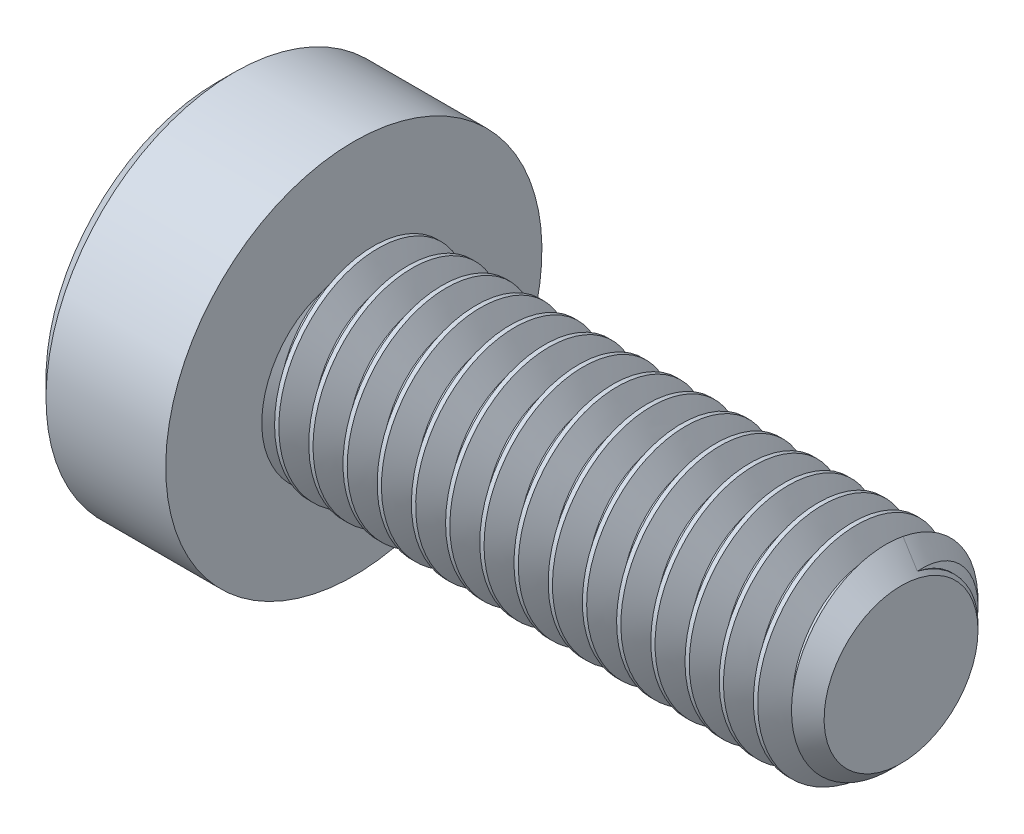
SolidWorks part; units mm, degrees
ref_plane "Front Plane" through (0, 0, 0) normal (0, 0, 1) x (1, 0, 0)
ref_plane "Top Plane" through (0, 0, 0) normal (0, 1, 0) x (1, 0, 0)
ref_plane "Right Plane" through (0, 0, 0) normal (1, 0, 0) x (0, 0, -1)
sketch "Sketch1" plane through (0, 0, 0) normal (0, 0, 1) x (1, 0, 0)
  line L0 (4, 0) -> (-4, 0) construction
  line L1 (4, 1.5) -> (4, -1.5) construction
  line L2 (-4, 2.75) -> (-4, -2.75) construction
  line L3 (-4, 2.75) -> (-5.75, 2.75) construction
  line L4 (-5.75, 2.75) -> (-6, 2.5) construction
  line L5 (-6, 2.5) -> (-6, -2.5) construction
  line L6 (-6, -2.5) -> (-5.75, -2.75) construction
  line L7 (-5.75, -2.75) -> (-4, -2.75) construction
  point P7 (-4.38, 0)
  point P12 (2, -1.5)
  dimension "D1" = 45
  dimension "Dec." = 3
  dimension "Length" = 8
  dimension "Head Dia" = 5.5
  dimension "Head Height" = 2
  dimension "Hex Depth" = 1.62
  dimension "Chamfer" = 0.25
  dimension "D2" = 2
ref_plane "Plane1" through (4, 0, 0) normal (1, 0, 0) x (0, 0, -1)
ref_plane "Plane2" through (-6, 0, 0) normal (1, 0, 0) x (0, 0, -1)
sketch "Sketch2" plane through (4, 0, 0) normal (1, 0, 0) x (0, 0, -1)
  circle A0 centre (0, 0) radius 1.5
extrude "Boss-Extrude1" add sketch "Sketch2" against normal up to vertex (8 mm away) up to point (-4, 0, 0)
sketch "Sketch3" plane through (4, 0, 0) normal (1, 0, 0) x (0, 0, -1)
  circle A0 centre (0, 0) radius 1.5 construction
  circle A1 centre (0, 0) radius 1.5
curve "Helix/Spiral1" pitch 0.5 height 8.5 radius 1.5 centre (4, 0, 0) axis (-1, 0, 0) start towards (0, 1, 0) parameters "Pitch"=0.5
chamfer "Chamfer1" distance 0.375 angle 45 1 edges at (4, 0, -1.5)
sketch "Sketch5" plane through (0, 0, 0) normal (0, 0, 1) x (1, 0, 0)
  line L0 (3.7813, 1.5) -> (4.2188, 1.5)
  line L1 (4.2188, 1.5) -> (4.0313, 1.1752)
  line L2 (4.0313, 1.1752) -> (3.9688, 1.1752)
  line L3 (3.9688, 1.1752) -> (3.7813, 1.5)
  line L4 (4, 1.1752) -> (4, 1.5) construction
  line L5 (3.875, 1.3376) -> (4.125, 1.3376) construction
  dimension "D1" = 60
  dimension "D2" = 0.25
  dimension "D3" = 0.0625
sweep "Cut-Sweep1" cut profiles "Sketch5" path "Helix/Spiral1" align with end faces yes
sketch "Sketch4" plane through (-6, 0, 0) normal (1, 0, 0) x (0, 0, -1)
  line L0 (-2.75, 0.7937) -> (2.75, 0.7937) construction
  line L1 (0, 1.1547) -> (-1, 0.5774)
  line L2 (-1, 0.5774) -> (-1, -0.5774)
  line L3 (-1, -0.5774) -> (0, -1.1547)
  line L4 (0, -1.1547) -> (1, -0.5774)
  line L5 (1, -0.5774) -> (1, 0.5774)
  line L6 (1, 0.5774) -> (0, 1.1547)
  line L7 (0, 0) -> (0, 0.7937) construction
  circle A0 centre (0, 0) radius 1 construction
  dimension "Hex Size" = 2
  dimension "D1" = 5.5
  dimension "D2" = 0.7937
sketch "Sketch6" plane through (0, 0, 0) normal (0, 0, 1) x (1, 0, 0)
  line L0 (-5.75, 2.75) -> (-6, 2.5) construction
  line L1 (-4, 2.75) -> (-5.75, 2.75) construction
  line L2 (-4, 2.75) -> (-4, -2.75) construction
  line L3 (-6, 2.5) -> (-6, -2.5) construction
  line L4 (-5.75, 2.75) -> (-6, 2.5)
  line L5 (-4, 2.75) -> (-5.75, 2.75)
  line L6 (-4, 2.75) -> (-4, 0)
  line L7 (-6, 2.5) -> (-6, 0)
  line L8 (-4, 0) -> (-6, 0) construction
  line L9 (-4, 0) -> (-6, 0)
revolve "Revolve1" add sketch "Sketch6" angle 360 about L8
extrude "Cut-Extrude1" cut sketch "Sketch4" along normal up to vertex (1.62 mm away) up to point (-4.38, 0, 0)
sketch "Sketch8" plane through (-6, 0, 0) normal (-1, 0, 0) x (0, 0, 1)
  circle A1 centre (0, 0) radius 1.1547
extrude "Cut-Extrude2" cut sketch "Sketch8" against normal through all draft 45
equation "\"D3@Helix/Spiral1\" = \"Length@Sketch1\"+\"Pitch@Helix/Spiral1\""
equation "\"D3@Sketch5\" = \"Pitch@Helix/Spiral1\"*.125"
equation "\"D2@Sketch5\" = \"Pitch@Helix/Spiral1\"*.50"
equation "\"D1@Chamfer1\" = \"Pitch@Helix/Spiral1\"*.75"
equation "\"D2@Sketch1\" = \"Pitch@Helix/Spiral1\"*4"
equation "\"D1@Sketch4\" = \"Head Dia@Sketch1\""
equation "\"Chamfer@Sketch1\" = \"Head Height@Sketch1\"/8"
